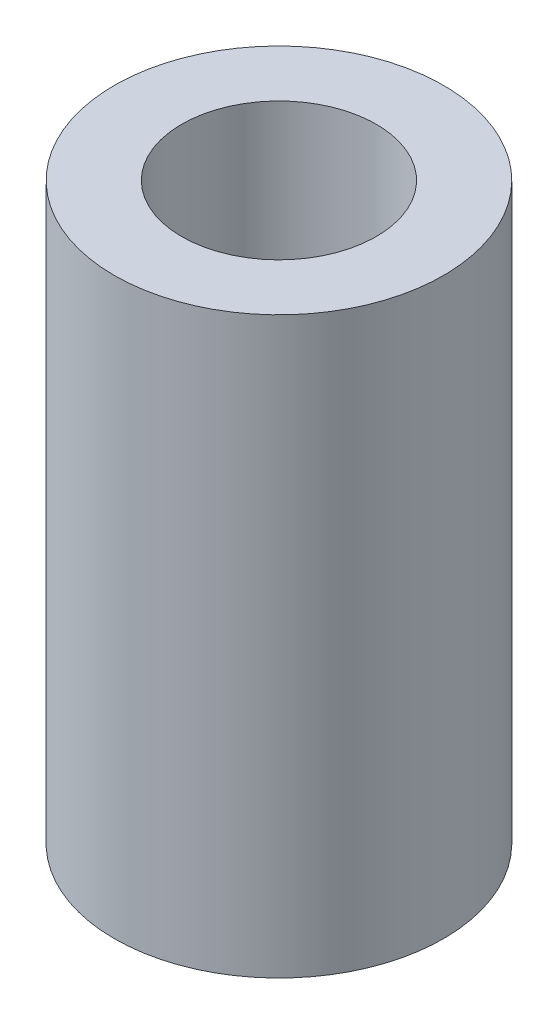
SolidWorks part; units mm, degrees
ref_plane "Front Plane" through (0, 0, 0) normal (0, 0, 1) x (1, 0, 0)
ref_plane "Top Plane" through (0, 0, 0) normal (0, 1, 0) x (1, 0, 0)
ref_plane "Right Plane" through (0, 0, 0) normal (1, 0, 0) x (0, 0, -1)
sketch "Sketch1" plane through (0, 0, 0) normal (0, 1, 0) x (1, 0, 0)
  circle A0 centre (0, 0) radius 20
  dimension "SLEEVE_OD" = 40
extrude "Boss-Extrude1" add sketch "Sketch1" along normal blind 69.7779
sketch "Sketch2" plane through (0, 0, 0) normal (0, 1, 0) x (1, 0, 0)
  circle A0 centre (0, 0) radius 11.8241
  dimension "BORE_D" = 23.6482
extrude "Cut-Extrude1" cut sketch "Sketch2" along normal through all
chamfer "Chamfer1" distance 3.0067 angle 60 rebuild error yes
